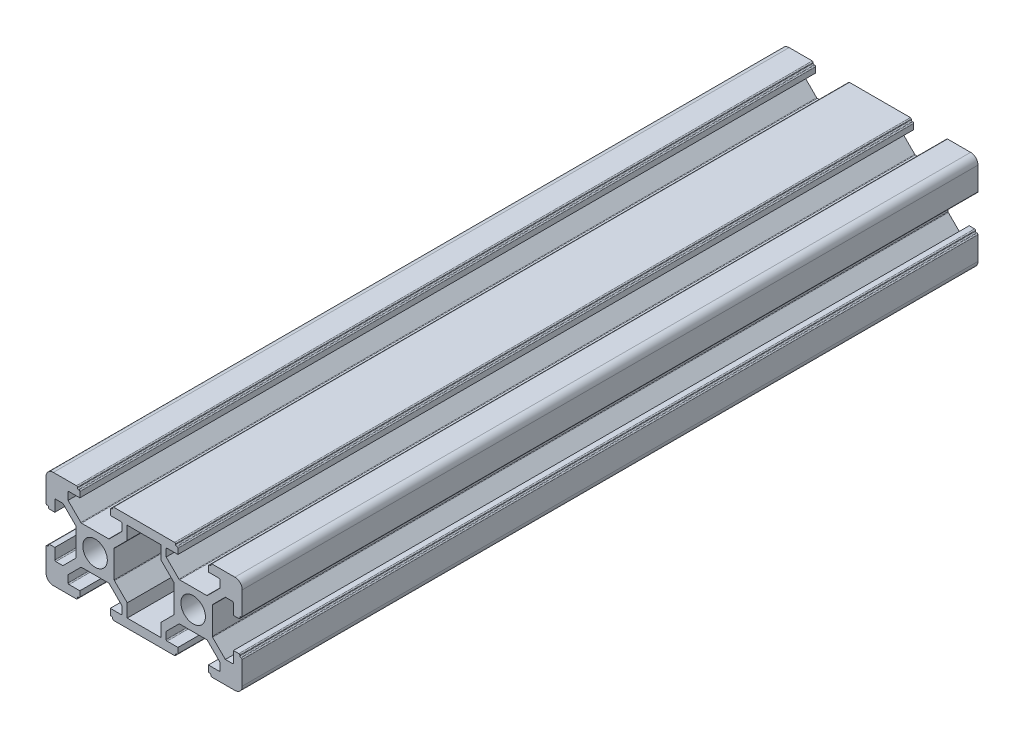
SolidWorks part; units mm, degrees
ref_plane "前视基准面" through (0, 0, 0) normal (0, 0, 1) x (1, 0, 0)
ref_plane "上视基准面" through (0, 0, 0) normal (0, 1, 0) x (1, 0, 0)
ref_plane "右视基准面" through (0, 0, 0) normal (1, 0, 0) x (0, 0, -1)
sketch "Sketch1" plane through (0, 0, 0) normal (0, 0, 1) x (1, 0, 0)
  line L0 (-8.5, 10) -> (-3.8, 10)
  line L3 (-8.5, -10) -> (-3.8, -10)
  line L5 (-10, 8.5) -> (-10, 3.8)
  line L6 (-2.7565, 3.9) -> (2.7565, 3.9)
  line L9 (-2.7565, -3.9) -> (2.7565, -3.9)
  line L10 (3.9, 2.7565) -> (3.9, -2.7565)
  line L11 (-3.9, 2.7565) -> (-3.9, -2.7565)
  line L12 (-3.9586, -2.8979) -> (-6.5607, -5.5)
  line L13 (3.6, 9.7) -> (3.6, 9.8)
  line L14 (3.1, -8.2) -> (5.3, -8.2)
  line L15 (-2.8979, -3.9586) -> (-5.5, -6.5607)
  line L16 (-3.1, -8.2) -> (-3.1, -9.3)
  line L17 (3.1, -8.2) -> (3.1, -9.3)
  line L18 (-5.5, -6.5607) -> (-5.5, -8)
  line L19 (5.5, -6.5607) -> (5.5, -8)
  line L20 (-5.3, -8.2) -> (-3.1, -8.2)
  line L21 (-3.4, -9.5) -> (-3.3, -9.5)
  line L22 (3.8, -10) -> (8.5, -10)
  line L23 (3.3, -9.5) -> (3.4, -9.5)
  line L24 (-3.6, -9.7) -> (-3.6, -9.8)
  line L25 (3.6, -9.7) -> (3.6, -9.8)
  line L26 (-6.5607, -5.5) -> (-8, -5.5)
  line L27 (-9.7, -3.6) -> (-9.8, -3.6)
  line L28 (-9.5, -3.4) -> (-9.5, -3.3)
  line L29 (-8.2, -3.1) -> (-9.3, -3.1)
  line L30 (-8.2, -5.3) -> (-8.2, -3.1)
  line L31 (-10, -3.8) -> (-10, -8.5)
  line L33 (3.8, 10) -> (8.5, 10)
  line L34 (2.8979, -3.9586) -> (5.5, -6.5607)
  line L40 (3.9586, -2.8979) -> (6.5607, -5.5)
  line L41 (3.3, 9.5) -> (3.4, 9.5)
  line L42 (30, 8.5) -> (30, 3.8)
  line L43 (3.1, 8.2) -> (3.1, 9.3)
  line L44 (3.1, 8.2) -> (5.3, 8.2)
  line L45 (5.5, 6.5607) -> (5.5, 8)
  line L46 (2.8979, 3.9586) -> (5.5, 6.5607)
  line L52 (3.9586, 2.8979) -> (6.5607, 5.5)
  line L53 (-3.6, 9.7) -> (-3.6, 9.8)
  line L54 (-3.4, 9.5) -> (-3.3, 9.5)
  line L55 (-3.1, 8.2) -> (-3.1, 9.3)
  line L56 (-5.3, 8.2) -> (-3.1, 8.2)
  line L57 (-5.5, 6.5607) -> (-5.5, 8)
  line L58 (-2.8979, 3.9586) -> (-5.5, 6.5607)
  line L59 (-9.5, 3.4) -> (-9.5, 3.3)
  line L60 (-9.7, 3.6) -> (-9.8, 3.6)
  line L61 (-8.2, 3.1) -> (-9.3, 3.1)
  line L62 (-8.2, 5.3) -> (-8.2, 3.1)
  line L63 (-6.5607, 5.5) -> (-8, 5.5)
  line L64 (-3.9586, 2.8979) -> (-6.5607, 5.5)
  line L65 (29.7, 3.6) -> (29.8, 3.6)
  line L66 (29.5, 3.4) -> (29.5, 3.3)
  line L67 (28.2, 3.1) -> (29.3, 3.1)
  line L68 (28.2, 5.3) -> (28.2, 3.1)
  line L69 (26.5607, 5.5) -> (28, 5.5)
  line L70 (23.9586, 2.8979) -> (26.5607, 5.5)
  line L71 (23.9, 2.7565) -> (23.9, -2.7565)
  line L72 (23.9586, -2.8979) -> (26.5607, -5.5)
  line L73 (26.5607, -5.5) -> (28, -5.5)
  line L74 (28.2, -5.3) -> (28.2, -3.1)
  line L75 (28.2, -3.1) -> (29.3, -3.1)
  line L76 (29.5, -3.4) -> (29.5, -3.3)
  line L77 (29.7, -3.6) -> (29.8, -3.6)
  line L78 (30, -3.8) -> (30, -8.5)
  line L79 (28.5, -10) -> (23.8, -10)
  line L80 (23.6, -9.7) -> (23.6, -9.8)
  line L81 (23.4, -9.5) -> (23.3, -9.5)
  line L82 (23.1, -8.2) -> (23.1, -9.3)
  line L83 (25.3, -8.2) -> (23.1, -8.2)
  line L84 (25.5, -6.5607) -> (25.5, -8)
  line L85 (22.8979, -3.9586) -> (25.5, -6.5607)
  line L86 (22.7565, -3.9) -> (17.2435, -3.9)
  line L87 (17.1021, -3.9586) -> (14.5, -6.5607)
  line L88 (14.5, -6.5607) -> (14.5, -8)
  line L89 (16.9, -8.2) -> (14.7, -8.2)
  line L90 (16.9, -8.2) -> (16.9, -9.3)
  line L91 (16.7, -9.5) -> (16.6, -9.5)
  line L92 (16.4, -9.7) -> (16.4, -9.8)
  line L93 (16.2, -10) -> (11.5, -10)
  line L94 (13.4393, 5.5) -> (13.4393, 8.2)
  line L96 (6.5607, 5.5) -> (6.5607, 8.2)
  line L97 (6.5607, 8.2) -> (13.4393, 8.2)
  line L99 (16.0414, -2.8979) -> (13.4393, -5.5)
  line L100 (16.1, 2.7565) -> (16.1, -2.7565)
  line L101 (16.0414, 2.8979) -> (13.4393, 5.5)
  line L107 (16.2, 10) -> (11.5, 10)
  line L108 (16.4, 9.7) -> (16.4, 9.8)
  line L109 (16.7, 9.5) -> (16.6, 9.5)
  line L110 (16.9, 8.2) -> (16.9, 9.3)
  line L111 (16.9, 8.2) -> (14.7, 8.2)
  line L112 (14.5, 6.5607) -> (14.5, 8)
  line L113 (17.1021, 3.9586) -> (14.5, 6.5607)
  line L114 (22.7565, 3.9) -> (17.2435, 3.9)
  line L115 (22.8979, 3.9586) -> (25.5, 6.5607)
  line L116 (25.5, 6.5607) -> (25.5, 8)
  line L117 (25.3, 8.2) -> (23.1, 8.2)
  line L118 (23.1, 8.2) -> (23.1, 9.3)
  line L119 (23.4, 9.5) -> (23.3, 9.5)
  line L120 (23.6, 9.7) -> (23.6, 9.8)
  line L121 (28.5, 10) -> (23.8, 10)
  line L122 (13.4393, -5.5) -> (13.4393, -8.2)
  line L124 (6.5607, -5.5) -> (6.5607, -8.2)
  line L125 (6.5607, -8.2) -> (13.4393, -8.2)
  line L127 (8.5, 10) -> (11.5, 10)
  line L128 (8.5, -10) -> (11.5, -10)
  arc A3 (-8.5, -10) -> (-10, -8.5) centre (-8.5, -8.5) cw
  arc A4 (-10, 8.5) -> (-8.5, 10) centre (-8.5, 8.5) cw
  arc A5 (3.4, -9.5) -> (3.6, -9.7) centre (3.4, -9.7) cw
  arc A6 (3.8, -10) -> (3.6, -9.8) centre (3.8, -9.8) cw
  arc A7 (3.3, -9.5) -> (3.1, -9.3) centre (3.3, -9.3) cw
  arc A8 (5.3, -8.2) -> (5.5, -8) centre (5.3, -8) ccw
  arc A9 (-3.9, -2.7565) -> (-3.9586, -2.8979) centre (-4.1, -2.7565) cw
  arc A10 (-3.9, 2.7565) -> (-3.9586, 2.8979) centre (-4.1, 2.7565) ccw
  arc A11 (-2.7565, 3.9) -> (-2.8979, 3.9586) centre (-2.7565, 4.1) cw
  arc A12 (2.7565, 3.9) -> (2.8979, 3.9586) centre (2.7565, 4.1) ccw
  arc A13 (3.9586, 2.8979) -> (3.9, 2.7565) centre (4.1, 2.7565) ccw
  arc A14 (3.9, -2.7565) -> (3.9586, -2.8979) centre (4.1, -2.7565) ccw
  arc A15 (-2.8979, -3.9586) -> (-2.7565, -3.9) centre (-2.7565, -4.1) cw
  arc A16 (2.7565, -3.9) -> (2.8979, -3.9586) centre (2.7565, -4.1) cw
  arc A17 (-3.6, -9.8) -> (-3.8, -10) centre (-3.8, -9.8) cw
  arc A18 (-3.3, -9.5) -> (-3.1, -9.3) centre (-3.3, -9.3) ccw
  arc A19 (-3.6, -9.7) -> (-3.4, -9.5) centre (-3.4, -9.7) cw
  arc A20 (-8.2, 5.3) -> (-8, 5.5) centre (-8, 5.3) cw
  arc A23 (-8.2, -5.3) -> (-8, -5.5) centre (-8, -5.3) ccw
  arc A24 (-5.3, -8.2) -> (-5.5, -8) centre (-5.3, -8) cw
  arc A31 (3.1, 9.3) -> (3.3, 9.5) centre (3.3, 9.3) cw
  arc A32 (3.6, 9.8) -> (3.8, 10) centre (3.8, 9.8) cw
  arc A33 (3.6, 9.7) -> (3.4, 9.5) centre (3.4, 9.7) cw
  arc A34 (-3.8, 10) -> (-3.6, 9.8) centre (-3.8, 9.8) cw
  arc A35 (-3.3, 9.5) -> (-3.1, 9.3) centre (-3.3, 9.3) cw
  arc A36 (-3.4, 9.5) -> (-3.6, 9.7) centre (-3.4, 9.7) cw
  arc A37 (5.5, 8) -> (5.3, 8.2) centre (5.3, 8) ccw
  arc A38 (-5.5, 8) -> (-5.3, 8.2) centre (-5.3, 8) cw
  arc A39 (-10, 3.8) -> (-9.8, 3.6) centre (-9.8, 3.8) ccw
  arc A40 (-9.5, 3.3) -> (-9.3, 3.1) centre (-9.3, 3.3) ccw
  arc A41 (-9.7, 3.6) -> (-9.5, 3.4) centre (-9.7, 3.4) cw
  arc A42 (-10, -3.8) -> (-9.8, -3.6) centre (-9.8, -3.8) cw
  arc A43 (-9.5, -3.3) -> (-9.3, -3.1) centre (-9.3, -3.3) cw
  arc A44 (-9.5, -3.4) -> (-9.7, -3.6) centre (-9.7, -3.4) cw
  arc A45 (30, 8.5) -> (28.5, 10) centre (28.5, 8.5) ccw
  arc A46 (30, 3.8) -> (29.8, 3.6) centre (29.8, 3.8) cw
  arc A47 (29.7, 3.6) -> (29.5, 3.4) centre (29.7, 3.4) ccw
  arc A48 (29.5, 3.3) -> (29.3, 3.1) centre (29.3, 3.3) cw
  arc A49 (28.2, 5.3) -> (28, 5.5) centre (28, 5.3) ccw
  arc A50 (23.9, 2.7565) -> (23.9586, 2.8979) centre (24.1, 2.7565) cw
  arc A51 (23.9, -2.7565) -> (23.9586, -2.8979) centre (24.1, -2.7565) ccw
  arc A52 (28.2, -5.3) -> (28, -5.5) centre (28, -5.3) cw
  arc A53 (29.5, -3.3) -> (29.3, -3.1) centre (29.3, -3.3) ccw
  arc A54 (29.5, -3.4) -> (29.7, -3.6) centre (29.7, -3.4) ccw
  arc A55 (30, -3.8) -> (29.8, -3.6) centre (29.8, -3.8) ccw
  arc A56 (28.5, -10) -> (30, -8.5) centre (28.5, -8.5) ccw
  arc A57 (23.6, -9.8) -> (23.8, -10) centre (23.8, -9.8) ccw
  arc A58 (23.6, -9.7) -> (23.4, -9.5) centre (23.4, -9.7) ccw
  arc A59 (23.3, -9.5) -> (23.1, -9.3) centre (23.3, -9.3) cw
  arc A60 (25.3, -8.2) -> (25.5, -8) centre (25.3, -8) ccw
  arc A61 (22.8979, -3.9586) -> (22.7565, -3.9) centre (22.7565, -4.1) ccw
  arc A62 (17.2435, -3.9) -> (17.1021, -3.9586) centre (17.2435, -4.1) ccw
  arc A63 (14.7, -8.2) -> (14.5, -8) centre (14.7, -8) cw
  arc A64 (16.7, -9.5) -> (16.9, -9.3) centre (16.7, -9.3) ccw
  arc A65 (16.6, -9.5) -> (16.4, -9.7) centre (16.6, -9.7) ccw
  arc A66 (16.2, -10) -> (16.4, -9.8) centre (16.2, -9.8) ccw
  arc A72 (16.1, -2.7565) -> (16.0414, -2.8979) centre (15.9, -2.7565) cw
  arc A73 (16.0414, 2.8979) -> (16.1, 2.7565) centre (15.9, 2.7565) cw
  arc A79 (16.4, 9.8) -> (16.2, 10) centre (16.2, 9.8) ccw
  arc A80 (16.4, 9.7) -> (16.6, 9.5) centre (16.6, 9.7) ccw
  arc A81 (16.9, 9.3) -> (16.7, 9.5) centre (16.7, 9.3) ccw
  arc A82 (14.5, 8) -> (14.7, 8.2) centre (14.7, 8) cw
  arc A83 (17.2435, 3.9) -> (17.1021, 3.9586) centre (17.2435, 4.1) cw
  arc A84 (22.7565, 3.9) -> (22.8979, 3.9586) centre (22.7565, 4.1) ccw
  arc A85 (25.5, 8) -> (25.3, 8.2) centre (25.3, 8) ccw
  arc A86 (23.3, 9.5) -> (23.1, 9.3) centre (23.3, 9.3) ccw
  arc A87 (23.4, 9.5) -> (23.6, 9.7) centre (23.4, 9.7) ccw
  arc A88 (23.8, 10) -> (23.6, 9.8) centre (23.8, 9.8) ccw
  point P11 (3.9, 3.9)
  point P19 (3.3697, 4.4303)
  point P20 (-10.6428, -10.6428)
  point P25 (-11.1731, -10.1124)
  point P26 (4.4303, 3.3697)
  point P28 (-10.1124, -11.1731)
  dimension "D3" = 0.2
  dimension "D4" = 0.2
  dimension "D5" = 0.2
  dimension "D8" = 0.2
  dimension "D9" = 0.2
  dimension "D10" = 0.2
  dimension "D6" = 1.8
  dimension "D7" = 0.5
extrude "Boss-Extrude1" add sketch "Sketch1" along normal blind 150
ref_plane "hole" through (0, 0, 150) normal (0, 0, 1) x (1, 0, 0)
sketch "Sketch2" plane through (0, 0, 150) normal (0, 0, 1) x (1, 0, 0)
  circle A0 centre (0, 0) radius 2.5
  circle A1 centre (20, 0) radius 2.5
  dimension "D1" = 5
extrude "Cut-Extrude1" cut sketch "Sketch2" against normal through all
sketch "Sketch3" plane through (23.9, 0, 0) normal (1, 0, 0) x (0, 0, -1)
  line L0 (-150, -2.7565) -> (-150, 2.7565) construction
  circle A0 centre (-133.3, 0) radius 1.5
  circle A1 centre (-116.6, 0) radius 1.5
  point P6 (-150, 0)
  dimension "D1" = 3
  dimension "D2" = 16.7
  dimension "D3" = 0
  dimension "D4" = 0
  dimension "D5" = 3
  dimension "D6" = 16.7
extrude "Cut-Extrude2" cut sketch "Sketch3" against normal blind 65
